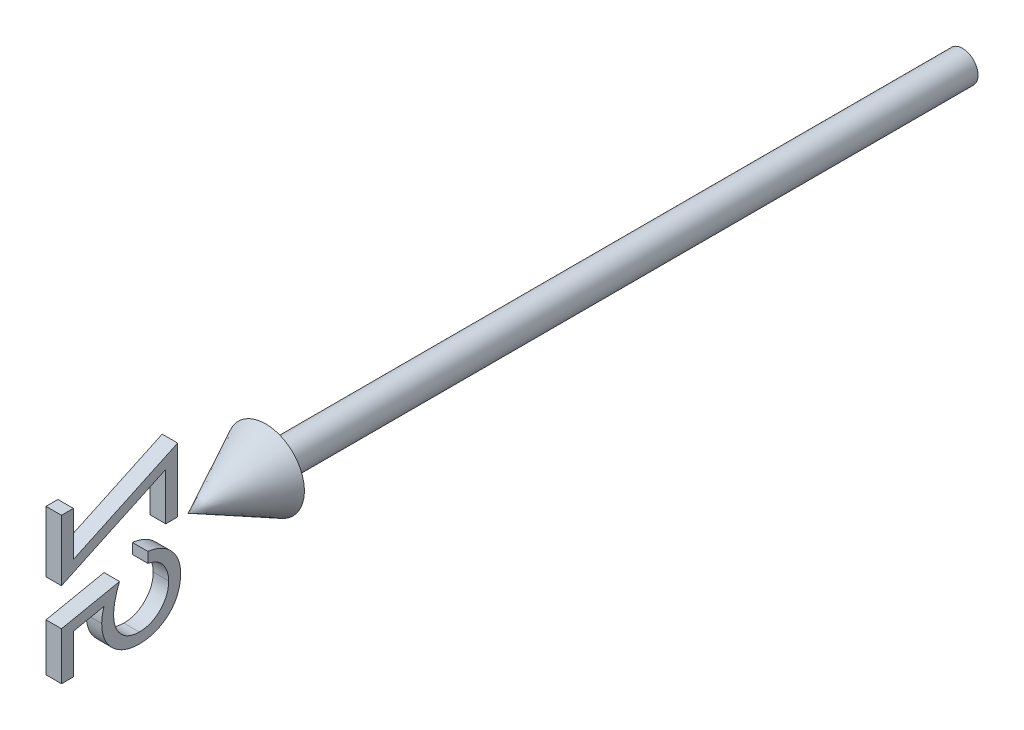
SolidWorks part; units mm, degrees
ref_plane "Front Plane" through (0, 0, 0) normal (0, 0, 1) x (1, 0, 0)
ref_plane "Top Plane" through (0, 0, 0) normal (0, 1, 0) x (1, 0, 0)
ref_plane "Right Plane" through (0, 0, 0) normal (1, 0, 0) x (0, 0, -1)
sketch "Sketch2" plane through (0, 0, 0) normal (0, 1, 0) x (1, 0, 0)
  line L0 (0, 41.95) -> (0, -114.4521) construction
  line L1 (-36.8894, 0) -> (41.4965, 0) construction
  line L2 (0, -100) -> (5, -90)
  line L3 (5, -90) -> (2, -90)
  line L4 (2, -90) -> (2, 0)
  line L5 (2, 0) -> (0, 0)
  line L6 (0, 0) -> (0, -100)
  dimension "D1" = 100
  dimension "D2" = 2
  dimension "D3" = 10
  dimension "D4" = 5
revolve "Revolve1" add sketch "Sketch2" angle 360 about L0
sketch "Sketch3" plane through (0, 0, 0) normal (1, 0, 0) x (0, -1, 0)
  line L0 (0, -101.5706) -> (0, -127.8138) construction
  line L1 (-10.1124, -102.3675) -> (14.1256, -102.3675) construction
  text T0 "Z5\r\n" font "Century Gothic" height 15
extrude "Boss-Extrude1" add sketch "Sketch3" against normal blind 1 and the other way blind 1 separate body
equation "\"frame_arrow_length\"=100"
equation "\"D1@Sketch2\"=\"frame_arrow_length\""
equation "\"frame_arrow_odA\"=4"
equation "\"D2@Sketch2\"=\"frame_arrow_odA\"/2"
equation "\"frame_arrow_head_od\"=5"
equation "\"D4@Sketch2\"=\"frame_arrow_head_od\""
equation "\"frame_arrow_head_length\"=10"
equation "\"D3@Sketch2\"=\"frame_arrow_head_length\""
equation "\"tvarobot_theta1\"=30"
equation "\"link0_ringA_odA\"= 40"
equation "\"link0_ringA_odB\"= 25"
equation "\"link0_ringA_id\"= 20"
equation "\"link0_ringA_thickness\"= (\"link0_ringA_odB\" - \"link0_ringA_id\")/2"
equation "\"link0_ringA_height\"= 3"
equation "\"link0_ringA_heightA\"= 1.5"
equation "\"link0_ringA_heightB\"=\"link0_ringA_height\"-\"link0_ringA_heightA\""
equation "\"link0_ringB_odA\"= 40"
equation "\"link0_ringB_odB\"= 29"
equation "\"link0_ringB_id\"= \"link0_shaftA_bearing_id\"+1"
equation "\"link0_ringB_thickness\"= (\"link0_ringB_odB\" - \"link0_ringB_id\")/2"
equation "\"link0_ringB_height\"= 3"
equation "\"link0_ringB_heightA\"= 1.5"
equation "\"link0_ringB_heightB\"=\"link0_ringB_height\"-\"link0_ringB_heightA\""
equation "\"link0_shaftA_bearing_od\"=27"
equation "\"link0_shaftA_bearing_id\"=20"
equation "\"link0_shaftA_thrust_bearing_od\"=35"
equation "\"link0_shaftA_thrust_bearing_id\"=20.04"
equation "\"link0_shaftA_retaining_ring_id\"=18.5"
equation "\"link0_shaftA_retaining_ring_groove_width\"=1.5"
equation "\"link0_shaftA_spline_length\"=8.0"
equation "\"link0_shaftA_spline_depth\"=1.0"
equation "\"link0_shaftA_spline_width\"=4.0"
equation "\"link0_shaftA_odA\"=\"link0_shaftA_bearing_id\""
equation "\"link0_shaftA_odB\"=35"
equation "\"link0_shaftA_odC\"=\"link0_shaftA_bearing_id\""
equation "\"link0_shaftA_odD\"=\"link0_shaftA_odC\"-2*\"link0_shaftA_spline_depth\""
equation "\"link0_shaftA_odE\"=\"link0_shaftA_bearing_id\""
equation "\"link0_shaftA_odF\"=\"link0_shaftA_odE\"-2*\"link0_shaftA_spline_depth\""
equation "\"link0_shaftA_idA\"=10"
equation "\"link0_shaftA_idB\"=6"
equation "\"link0_shaftA_length\"=39.5"
equation "\"link0_shaftA_lengthA\"=8.0"
equation "\"link0_shaftA_lengthB\"=12.0"
equation "\"link0_shaftA_lengthC\"=35.0"
equation "\"link0_shaftA_lengthD\"=39.0"
equation "\"link0_shaftA_lengthE\"=\"link0_shaftA_length\"-\"link0_shaftA_lengthD\""
equation "\"link0_shaftA_offsetX\"=11"
equation "\"link0_shaftA_offsetY\"=0"
equation "\"link0_shaftA_bolt_pattern_dia\"=14"
equation "\"link0_motor_center_dist\"=26"
equation "\"link0_46t_pulley_spline_length\"=8"
equation "\"link0_46t_pulley_spline_depth\"=\"link0_shaftA_spline_depth\"*1.025"
equation "\"link0_46t_pulley_spline_width\"=\"link0_shaftA_spline_width\"*1.05"
equation "\"link0_46t_pulley_idA\"=\"link0_shaftA_bearing_id\"*1.025"
equation "\"link0_46t_pulley_idB\"=\"link0_46t_pulley_idA\"-2*\"link0_46t_pulley_spline_depth\""
equation "\"link0_shaftB_spline_length\"=10"
equation "\"link0_shaftB_spline_depth\"=1.0"
equation "\"link0_shaftB_spline_width\"=1.25"
equation "\"link0_shaftB_length\"=7"
equation "\"link0_shaftB_lengthA\"=1.5"
equation "\"link0_shaftB_lengthB\"=2.75"
equation "\"link0_shaftB_odA\"=32"
equation "\"link0_shaftB_odB\"=22"
equation "\"link0_shaftB_odC\"=20"
equation "\"link0_shaftB_idA\"=10"
equation "\"link0_shaftB_bolt_diameter\"=19"
equation "\"link0_shaftB_bearing_od\"=27"
equation "\"link0_shaftB_bearing_id\"=20"
equation "\"link0_motor_length\"=46.5"
equation "\"link0_motor_width\"=28.5"
equation "\"link0_motor_height\"=34"
equation "\"link0_motor_offset\"=8"
equation "\"link0_shellA_thickness\"=2.5"
equation "\"link0_shellB_thickness\"=\"link0_shellA_thickness\""
equation "\"link0_plateA_shellA_height\"=48"
equation "\"link0_shellA_width\" =\"link0_plateA_width\""
equation "\"link0_shellA_height\" = \"link0_plateA_shellA_height\"-\"link0_plateA_height\""
equation "\"link0_shellA_length\" = \"link0_plateA_lengthB\" "
equation "\"link0_shellB_length\"=\"link0_shellA_length\""
equation "\"link0_shellA_radius\" = 0.375*25.4"
equation "\"link0_shellA_radiusA\"= \"link0_plateA_radiusA\""
equation "\"link0_shellA_radiusB\"= \"link0_plateA_radiusB\""
equation "\"link0_shellA_radiusC\"= 3"
equation "\"link0_postA_height\"=7"
equation "\"link0_postA_width\"=16"
equation "\"link0_postA_length\"=20"
equation "\"link0_postA_posX\"=22"
equation "\"link0_postA_posY\"=17.5"
equation "\"link0_postA_pocket_width\"=6.0"
equation "\"link0_postA_pocket_length\"=2.5"
equation "\"link0_postA_pocket_depth\"=9"
equation "\"link0_postA_pocket_posZ\"=10"
equation "\"link0_postB_height\"=7"
equation "\"link0_postB_width\"=16"
equation "\"link0_postB_length\"=20"
equation "\"link0_postB_posX\"=22"
equation "\"link0_postB_posY\"=17.5"
equation "\"link0_postB_id\"=3.0"
equation "\"link0_postB_pocket_width\"=6.0"
equation "\"link0_postB_pocket_length\"=2.5"
equation "\"link0_postB_pocket_depth\"=9"
equation "\"link0_postB_pocket_posZ\"=10"
equation "\"link0_postC_height\"=7"
equation "\"link0_postC_width\"=16"
equation "\"link0_postC_length\"=20"
equation "\"link0_postC_posX\"=22"
equation "\"link0_postC_posY\"=17.5"
equation "\"link0_postC_id\"=3.0"
equation "\"link0_postC_pocket_width\"=6.0"
equation "\"link0_postC_pocket_length\"=2.5"
equation "\"link0_postC_pocket_depth\"=9"
equation "\"link0_postC_pocket_posZ\"=10"
equation "\"link0_postD_height\"=7"
equation "\"link0_postD_width\"=16"
equation "\"link0_postD_length\"=20"
equation "\"link0_postD_posX\"=22"
equation "\"link0_postD_posY\"=17.5"
equation "\"link0_postD_id\"=3.0"
equation "\"link0_postD_pocket_width\"=6.0"
equation "\"link0_postD_pocket_length\"=3.0"
equation "\"link0_postD_pocket_depth\"=9"
equation "\"link0_postD_pocket_posZ\"=10"
equation "\"link0_postE_height\"=5"
equation "\"link0_postE_width\"=16"
equation "\"link0_postE_length\"=\"link0_plateE_lengthA\"-\"link0_lip_height\""
equation "\"link0_postE_posZ\"=22"
equation "\"link0_postE_posX\"=17.5"
equation "\"link0_postE_posY\"=22"
equation "\"link0_postE_id\"=3.0"
equation "\"link0_postE_cbore_id\"=6.5"
equation "\"link0_postE_hole_id\"=3"
equation "\"link0_postF_posZ\"=22"
equation "\"link0_postF_posX\"=17.5"
equation "\"link0_postF_posY\"=\"link0_plateB_lengthA\"+4"
equation "\"link0_postF_id\"=3.0"
equation "\"link0_postF_cbore_id\"=6.5"
equation "\"link0_postF_hole_id\"=3"
equation "\"link0_postG_posZ\"=22"
equation "\"link0_postG_posX\"=17.5"
equation "\"link0_postG_posY\"=\"link0_plateB_lengthA\"+12"
equation "\"link0_postG_id\"=3.0"
equation "\"link0_postG_cbore_id\"=6.5"
equation "\"link0_postG_hole_id\"=3"
equation "\"link0_postHIJ_posY\"=6"
equation "\"link0_postH_posX\"=28"
equation "\"link0_postH_posY\"=20"
equation "\"link0_postH_posZ\"=20"
equation "\"link0_postH_length\"=10"
equation "\"link0_postI_posX\"=28"
equation "\"link0_postI_posY\"=20"
equation "\"link0_postI_posZ\"=135"
equation "\"link0_postI_length\"=10"
equation "\"link0_postJ_posX\"=28"
equation "\"link0_postJ_posY\"=20"
equation "\"link0_postJ_posZ\"=175"
equation "\"link0_postJ_length\"=10"
equation "\"link0_postK_posX\"=28"
equation "\"link0_postK_posY\"=20"
equation "\"link0_postK_posZ\"=175"
equation "\"link0_postK_length\"=10"
equation "\"link0_postL_posX\"=28"
equation "\"link0_postL_posY\"=20"
equation "\"link0_postL_posZ\"=135"
equation "\"link0_postL_length\"=10"
equation "\"link0_postM_posX\"=28"
equation "\"link0_postM_posY\"=20"
equation "\"link0_postM_posZ\"=35"
equation "\"link0_postM_length\"=10"
equation "\"link0_plateA_lengthA\"=30"
equation "\"link0_plateA_lengthB\"=150"
equation "\"link0_plateA_lengthC\"=30"
equation "\"link0_plateA_length\"=\"link0_plateA_lengthA\"+\"link0_plateA_lengthB\"+\"link0_plateA_lengthC\""
equation "\"link0_plateA_width\"=  68"
equation "\"link0_plateA_height\"= \"link0_plateA_radiusA\""
equation "\"link0_plateA_thickness\"=\"link0_shellA_thickness\""
equation "\"link0_plateA_radius\"= 9.5"
equation "\"link0_plateA_radiusA\"= 18"
equation "\"link0_plateA_radiusB\"= 18"
equation "\"link0_plateA_radiusC\"= 3"
equation "\"link0_plateB_length\"= 40"
equation "\"link0_plateB_width\"= \"link0_plateA_width\"*1.005"
equation "\"link0_plateB_height\"= \"link0_plateA_shellA_height\"*1.005"
equation "\"link0_plateB_lengthA\"=\"link0_lip_height\"+\"link0_plateD_thickness\"+\"link0_motor_mount_thickness\""
equation "\"link0_plateB_lengthB\"=\"link0_plateB_height\"-\"link0_plateB_lengthA\""
equation "\"link0_plateB_radiusA\"= \"link0_plateA_radiusA\""
equation "\"link0_plateB_radiusB\"= \"link0_plateA_radiusB\""
equation "\"link0_plateB_radiusC\"= 3"
equation "\"link0_plateB_idA\"=\"link0_shaftA_odC\"+1"
equation "\"link0_plateB_idB\"=\"link0_shaftA_bearing_od\"-2"
equation "\"link0_plateB_idC\"=\"link0_shaftA_bearing_od\"*1.005"
equation "\"link0_plateB_idD\"=\"link0_shaftA_thrust_bearing_od\"+1 "
equation "\"link0_plateB_depthA\"=1.0"
equation "\"link0_plateB_depthB\"=2.0"
equation "\"link0_plateB_depthC\"=8"
equation "\"link0_plateB_depthD\"=\"link0_plateB_length\"-\"link0_lip_height\"-\"link0_plateD_thickness\" "
equation "\"link0_plateC_length\"=\"link0_plateB_length\""
equation "\"link0_plateC_width\"= \"link0_plateB_width\""
equation "\"link0_plateC_height\"= .1*25.4"
equation "\"link0_plateA_hole_od\" = 0.1*25.4"
equation "\"link0_plateA_hole_delx\" = 0.5*25.4"
equation "\"link0_plateA_hole_delz\" = 0.75*25.4"
equation "\"link0_plateA_hole_offx\" = 0.0*25.4"
equation "\"link0_plateA_hole_offz\" = \"link0_plateA_length\"/2"
equation "\"link0_plateB_hole_od\" = 0.1*25.4"
equation "\"link0_plateB_hole_delx\"= 0.75*25.4"
equation "\"link0_plateB_hole_delz\"= 0.75*25.4"
equation "\"link0_plateB_hole_offx\"= 0.0*25.4"
equation "\"link0_plateB_hole_offz\"= 0.0*25.4"
equation "\"link0_plateC_hole_od\"= 0.1*25.4"
equation "\"link0_plateC_hole_delx\"= 0.75*25.4"
equation "\"link0_plateC_hole_delz\"= 0.75*25.4"
equation "\"link0_plateC_hole_offx\"= 0.0*25.4"
equation "\"link0_plateC_hole_offz\"= 0.0*25.4"
equation "\"link0_plateD_height\"=\"link0_plateB_height\"-2*\"link0_shellA_thickness\""
equation "\"link0_plateD_width\"=\"link0_plateB_width\"-2*\"link0_shellA_thickness\""
equation "\"link0_plateD_thickness\"=10"
equation "\"link0_plateD_radiusA\"=\"link0_plateB_radiusA\"-\"link0_shellA_thickness\""
equation "\"link0_plateD_odA\"= .375*25.4"
equation "\"link0_plateD_odB\"= .375*25.4"
equation "\"link0_plateD_bearing_id\"=20"
equation "\"link0_plateD_bearing_od\"=27"
equation "\"link0_plateE_radiusA\"=\"link0_plateA_radiusA\""
equation "\"link0_plateE_radiusB\"=\"link0_plateA_radiusB\""
equation "\"link0_plateE_radiusC\"=8.0"
equation "\"link0_plateE_length\"=30"
equation "\"link0_plateE_lengthA\"=16"
equation "\"link0_plateE_height\"=\"link0_plateB_height\""
equation "\"link0_plateE_width\"=\"link0_plateB_width\""
equation "\"link0_plateE_odA\"=\"gantry_coupler_id\"*0.99"
equation "\"link0_plateE_idA\"=\"link0_plateE_odA\"-20.0"
equation "\"link0_plateE_spline_depth\"=\"link0_poleA_spline_depth\"*1.05"
equation "\"link0_plateE_spline_width\"=\"link0_poleA_spline_width\"*1.075"
equation "\"link0_plateE_spline_length\"=\"link0_poleA_spline_length\""
equation "\"link0_plateE_coupler_length\"=46"
equation "\"link0_lip_height\"=5.0"
equation "\"link0_lip_thickness\"=2.0"
equation "\"link0_motor_mount_thickness\"=8.0"
equation "\"link0_motor_mount_idA\"=22"
equation "\"link0_motor_mount_idB\"=\"link0_shaftB_bearing_od\"*1.005"
equation "\"link0_motor_mount_idC\"=\"link0_shaftB_bearing_od\"-2"
equation "\"link0_motor_mount_depthA\"=5.5"
equation "\"link0_motor_mount_height\"=\"link0_plateD_height\""
equation "\"link0_motor_mount_width\"=\"link0_plateD_width\""
equation "\"link0_motor_mountL_height\"=36"
equation "\"link0_motor_mountL_heightA\"=12"
equation "\"link0_motor_mountL_length\"=50"
equation "\"link0_motor_mountL_lengthA\"=36"
equation "\"gantry_coupler_od\"=25.4*2.0"
equation "\"gantry_coupler_id\"=1.645*25.4"
equation "\"gantry_coupler_offsetX\"=\"link0_plateE_width\"/2"
equation "\"link0_poleA_odA\"=20"
equation "\"link0_poleA_odB\"=36"
equation "\"link0_poleA_idA\"=\"link0_poleA_odA\"-2*\"link0_poleA_thickness\""
equation "\"link0_poleA_idB\"=(\"link0_plateE_idA\"/2+1.5*\"link0_lip_thickness\")*1.04"
equation "\"link0_poleA_thickness\"=3.5"
equation "\"link0_poleA_length\"=100"
equation "\"link0_poleA_lengthA\"=18.5"
equation "\"link0_poleA_lengthB\"=80"
equation "\"link0_poleA_gasket_thickness\"=1.5"
equation "\"link0_poleA_spline_depth\"=1.0"
equation "\"link0_poleA_spline_width\"=4.0"
equation "\"link0_poleA_spline_length\"=10.0"
equation "\"link1_plateB_length\"=30"
equation "\"link1_lip_height\"=\"link0_lip_height\""
equation "\"link0_tension_plateA_width\"=12"
equation "\"link0_tension_plateA_lengthA\"=10.5"
equation "\"link0_tension_plateB_width\"=\"link0_tension_plateA_width\""
equation "\"link0_tension_plateB_lengthA\"=\"link0_tension_plateA_lengthA\""
equation "\"link0_tension_wheelA_posZ\"=7"
equation "\"link0_tension_wheelA_posX\"=\"link0_plateD_height\"/2-\"link0_tension_plateA_lengthA\""
equation "\"link0_m2_clear_hole_id\"=2.35"
equation "\"link0_m2_insert_hole_id\"=2.5"
equation "\"link0_m2_tap_hole_id\"=1.75"
equation "\"link0_m2_nut_socket_width\"=4.25"
equation "\"link0_m2_nut_socket_depth\"=2.5"
equation "\"link0_m2_cbore_id\"=3.75"
equation "\"link0_m2_cbore_depth\"=7"
equation "\"link0_m2_5_clear_hole_id\"=2.75"
equation "\"link0_m2_5_insert_hole_id\"=2.75"
equation "\"link0_m2_5_tap_hole_id\"=2.25"
equation "\"link0_m2_5_nut_socket_width\"=5.25"
equation "\"link0_m2_5_nut_socket_depth\"=2.5"
equation "\"link0_m2_5_cbore_id\"=4.75"
equation "\"link0_m2_5_cbore_depth\"=2.5"
equation "\"link0_m2_5_insert_access_length\"=6.0"
equation "\"link0_m2_5_insert_access_width\"=3.0"
equation "\"link0_m3_clear_hole_id\"=3.25"
equation "\"link0_m3_insert_hole_id\"=3"
equation "\"link0_m3_tap_hole_id\"=2.75"
equation "\"link0_m3_nut_socket_width\"=5.75"
equation "\"link0_m3_nut_socket_depth\"=4.0"
equation "\"link0_m3_cbore_id\"=5.75"
equation "\"link0_m3_cbore_depth\"=3.5"
equation "\"link0_m3_insert_access_length\"=4.5"
equation "\"link0_m3_insert_access_width\"=3.5"
equation "\"link0_rpi_mount_height\"=6"
equation "\"link0_rpi_mount_width\"=49"
equation "\"link0_rpi_mount_length\"=58"
equation "\"link0_rpi_mount_post_od\"=6"
equation "\"link0_rpi_mount_posZ\"=72"
equation "\"link0_rpi_mount_posX\"=11.5"
equation "\"link0_mcu_mount_height\"=5"
equation "\"link0_mcu_mount_width\"=49"
equation "\"link0_mcu_mount_length\"=58"
equation "\"link0_mcu_mount_post_od\"=6"
equation "\"link0_mcu_mount_posZ\"=164"
equation "\"link0_mcu_mount_posX\"=4"
equation "\"link0_pwr_mount_height\"=4"
equation "\"link0_pwr_mount_width\"=15.75"
equation "\"link0_pwr_mount_length\"=75.75"
equation "\"link0_pwr_mount_post_od\"=6"
equation "\"link0_pwr_mount_posZ\"=75"
equation "\"link0_pwr_mount_posX\"=16"
equation "\"link0_pwr_board_height\"=6"
equation "\"link0_pwr_board_width\"=21"
equation "\"link0_pwr_board_length\"=80"
